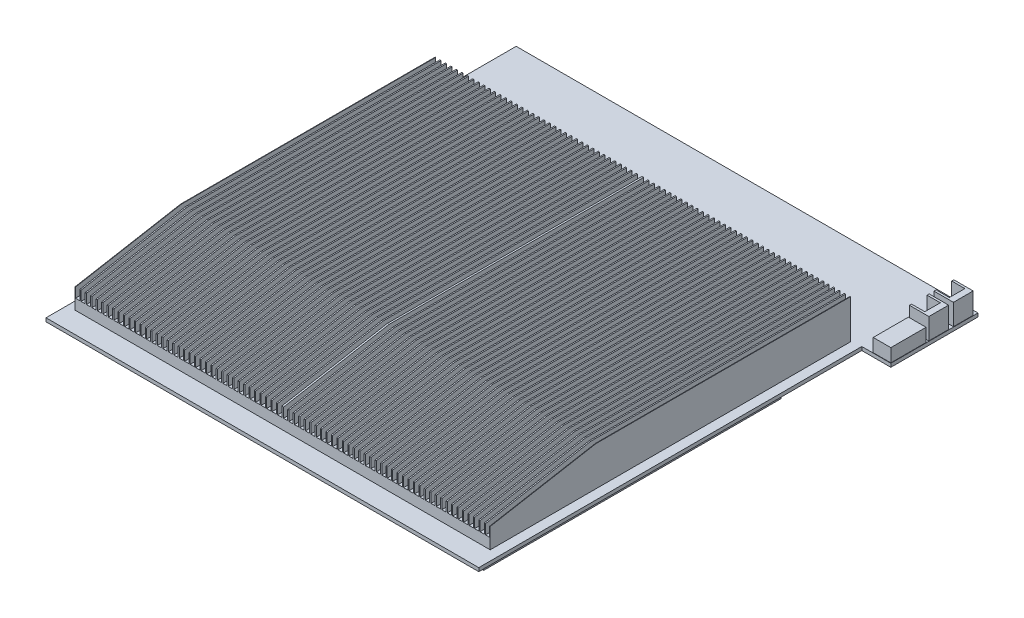
SolidWorks part; units mm, degrees
ref_plane "Front Plane" through (0, 0, 0) normal (0, 0, 1) x (1, 0, 0)
ref_plane "Top Plane" through (0, 0, 0) normal (0, 1, 0) x (1, 0, 0)
ref_plane "Right Plane" through (0, 0, 0) normal (1, 0, 0) x (0, 0, -1)
sketch "Sketch1" plane through (0, 0, 0) normal (0, 1, 0) x (1, 0, 0)
  line L0 (0, 0) -> (0, 267)
  line L1 (0, 267) -> (262.25, 267)
  line L2 (262.25, 267) -> (262.25, 217.5)
  line L3 (262.25, 217.5) -> (245.75, 217.5)
  line L4 (245.75, 217.5) -> (245.75, 0)
  line L5 (245.75, 0) -> (0, 0)
  dimension "D1" = 267
  dimension "D2" = 245.75
  dimension "D3" = 49.5
  dimension "D4" = 16.5
extrude "Boss-Extrude1" add sketch "Sketch1" along normal blind 2
sketch "Sketch2" plane through (0, 2, 0) normal (0, 1, 0) x (1, 0, 0)
  line L0 (245.75, 0) -> (245.75, 217.5) construction
  line L1 (4.5, 216.5) -> (240.25, 216.5)
  line L2 (4.5, 216.5) -> (4.5, 12)
  line L3 (4.5, 12) -> (240.25, 12)
  line L4 (240.25, 216.5) -> (240.25, 12)
  line L5 (4.5, 216.5) -> (240.25, 12) construction
  line L6 (4.5, 12) -> (240.25, 216.5) construction
  line L7 (0, 0) -> (245.75, 0) construction
  line L8 (0, 267) -> (0, 0) construction
  line L9 (262.25, 267) -> (0, 267) construction
  point P4 (122.375, 114.25)
  dimension "D1" = 5.5
  dimension "D2" = 12
  dimension "D3" = 4.5
  dimension "D4" = 50.5
extrude "Boss-Extrude2" add sketch "Sketch2" along normal blind 22.2
sketch "Sketch3" plane through (240.25, 0, 0) normal (1, 0, 0) x (0, 0, -1)
  line L0 (12, 13.5) -> (72, 24.2)
  line L1 (12, 24.2) -> (12, 2) construction
  line L2 (12, 24.2) -> (216.5, 24.2) construction
  line L3 (72, 24.2) -> (12, 24.2)
  line L4 (12, 24.2) -> (12, 13.5)
  dimension "D1" = 60
  dimension "D2" = 10.7
extrude "Cut-Extrude1" cut sketch "Sketch3" against normal up to surface (235.75 mm away) up to face at (4.5, 13.1, -114.25)
sketch "Sketch5" plane through (0, 0, 0) normal (0, -1, 0) x (1, 0, 0)
  line L0 (7.9691, -183.75) -> (7.9691, -14.75)
  line L6 (233.7585, -14.75) -> (233.7585, -183.75)
  line L9 (7.9691, -183.75) -> (67.4691, -183.75)
  line L10 (67.4691, -183.75) -> (67.4691, -216.5)
  line L11 (67.4691, -216.5) -> (174.2585, -216.5)
  line L12 (174.2585, -216.5) -> (174.2585, -183.75)
  line L13 (174.2585, -183.75) -> (233.7585, -183.75)
  line L14 (233.7585, -14.75) -> (7.9691, -14.75)
  line L15 (0, 0) -> (245.75, 0) construction
  line L16 (262.25, -267) -> (0, -267) construction
  line L18 (122.5508, -231.25) -> (149.8508, -231.25)
  line L19 (122.5508, -231.25) -> (122.5508, -261.5)
  line L20 (122.5508, -261.5) -> (149.8508, -261.5)
  line L21 (149.8508, -231.25) -> (149.8508, -261.5)
  line L22 (122.5508, -231.25) -> (149.8508, -261.5) construction
  line L23 (122.5508, -261.5) -> (149.8508, -231.25) construction
  point P16 (136.2008, -246.375)
  dimension "D1" = 14.75
  dimension "D2" = 50.5
  dimension "D3" = 83.25
  dimension "D4" = 59.5
  dimension "D5" = 5.5
  dimension "D6" = 14.75
  dimension "D7" = 27.3
extrude "Boss-Extrude4" add sketch "Sketch5" along normal blind 12.75
sketch "Sketch6" plane through (0, 0, -216.5) normal (0, 0, -1) x (-1, 0, 0)
  line L0 (-122.375, 24.2) -> (-122.375, 2) construction
  line L1 (-240.25, 24.2) -> (-4.5, 24.2) construction
  line L2 (-240.25, 2) -> (-4.5, 2) construction
  line L3 (-262.25, 2) -> (0, 2) construction
  line L4 (-122.875, 24.2) -> (-125.275, 24.2)
  line L5 (-122.875, 24.2) -> (-122.875, 8)
  line L6 (-122.875, 8) -> (-125.275, 8)
  line L7 (-125.275, 24.2) -> (-125.275, 8)
  line L8 (-122.875, 24.2) -> (-125.275, 8) construction
  line L9 (-122.875, 8) -> (-125.275, 24.2) construction
  line L10 (-121.875, 8) -> (-119.475, 24.2) construction
  line L11 (-121.875, 24.2) -> (-119.475, 8) construction
  line L12 (-119.475, 24.2) -> (-119.475, 8)
  line L13 (-121.875, 8) -> (-119.475, 8)
  line L14 (-121.875, 24.2) -> (-121.875, 8)
  line L15 (-121.875, 24.2) -> (-119.475, 24.2)
  line L16 (-125.975, 24.2) -> (-128.375, 24.2)
  line L17 (-125.975, 24.2) -> (-125.975, 8)
  line L18 (-125.975, 8) -> (-128.375, 8)
  line L19 (-128.375, 24.2) -> (-128.375, 8)
  line L20 (-125.975, 24.2) -> (-128.375, 8) construction
  line L21 (-125.975, 8) -> (-128.375, 24.2) construction
  line L22 (-129.075, 24.2) -> (-131.475, 24.2)
  line L23 (-129.075, 24.2) -> (-129.075, 8)
  line L24 (-129.075, 8) -> (-131.475, 8)
  line L25 (-131.475, 24.2) -> (-131.475, 8)
  line L26 (-129.075, 24.2) -> (-131.475, 8) construction
  line L27 (-129.075, 8) -> (-131.475, 24.2) construction
  line L28 (-132.175, 24.2) -> (-134.575, 24.2)
  line L29 (-132.175, 24.2) -> (-132.175, 8)
  line L30 (-132.175, 8) -> (-134.575, 8)
  line L31 (-134.575, 24.2) -> (-134.575, 8)
  line L32 (-132.175, 24.2) -> (-134.575, 8) construction
  line L33 (-132.175, 8) -> (-134.575, 24.2) construction
  line L34 (-135.275, 24.2) -> (-137.675, 24.2)
  line L35 (-135.275, 24.2) -> (-135.275, 8)
  line L36 (-135.275, 8) -> (-137.675, 8)
  line L37 (-137.675, 24.2) -> (-137.675, 8)
  line L38 (-135.275, 24.2) -> (-137.675, 8) construction
  line L39 (-135.275, 8) -> (-137.675, 24.2) construction
  line L40 (-138.375, 24.2) -> (-140.775, 24.2)
  line L41 (-138.375, 24.2) -> (-138.375, 8)
  line L42 (-138.375, 8) -> (-140.775, 8)
  line L43 (-140.775, 24.2) -> (-140.775, 8)
  line L44 (-138.375, 24.2) -> (-140.775, 8) construction
  line L45 (-138.375, 8) -> (-140.775, 24.2) construction
  line L46 (-141.475, 24.2) -> (-143.875, 24.2)
  line L47 (-141.475, 24.2) -> (-141.475, 8)
  line L48 (-141.475, 8) -> (-143.875, 8)
  line L49 (-143.875, 24.2) -> (-143.875, 8)
  line L50 (-141.475, 24.2) -> (-143.875, 8) construction
  line L51 (-141.475, 8) -> (-143.875, 24.2) construction
  line L52 (-144.575, 24.2) -> (-146.975, 24.2)
  line L53 (-144.575, 24.2) -> (-144.575, 8)
  line L54 (-144.575, 8) -> (-146.975, 8)
  line L55 (-146.975, 24.2) -> (-146.975, 8)
  line L56 (-144.575, 24.2) -> (-146.975, 8) construction
  line L57 (-144.575, 8) -> (-146.975, 24.2) construction
  line L58 (-147.675, 24.2) -> (-150.075, 24.2)
  line L59 (-147.675, 24.2) -> (-147.675, 8)
  line L60 (-147.675, 8) -> (-150.075, 8)
  line L61 (-150.075, 24.2) -> (-150.075, 8)
  line L62 (-147.675, 24.2) -> (-150.075, 8) construction
  line L63 (-147.675, 8) -> (-150.075, 24.2) construction
  line L64 (-150.775, 24.2) -> (-153.175, 24.2)
  line L65 (-150.775, 24.2) -> (-150.775, 8)
  line L66 (-150.775, 8) -> (-153.175, 8)
  line L67 (-153.175, 24.2) -> (-153.175, 8)
  line L68 (-150.775, 24.2) -> (-153.175, 8) construction
  line L69 (-150.775, 8) -> (-153.175, 24.2) construction
  line L70 (-153.875, 24.2) -> (-156.275, 24.2)
  line L71 (-153.875, 24.2) -> (-153.875, 8)
  line L72 (-153.875, 8) -> (-156.275, 8)
  line L73 (-156.275, 24.2) -> (-156.275, 8)
  line L74 (-153.875, 24.2) -> (-156.275, 8) construction
  line L75 (-153.875, 8) -> (-156.275, 24.2) construction
  line L76 (-156.975, 24.2) -> (-159.375, 24.2)
  line L77 (-156.975, 24.2) -> (-156.975, 8)
  line L78 (-156.975, 8) -> (-159.375, 8)
  line L79 (-159.375, 24.2) -> (-159.375, 8)
  line L80 (-156.975, 24.2) -> (-159.375, 8) construction
  line L81 (-156.975, 8) -> (-159.375, 24.2) construction
  line L82 (-160.075, 24.2) -> (-162.475, 24.2)
  line L83 (-160.075, 24.2) -> (-160.075, 8)
  line L84 (-160.075, 8) -> (-162.475, 8)
  line L85 (-162.475, 24.2) -> (-162.475, 8)
  line L86 (-160.075, 24.2) -> (-162.475, 8) construction
  line L87 (-160.075, 8) -> (-162.475, 24.2) construction
  line L88 (-163.175, 24.2) -> (-165.575, 24.2)
  line L89 (-163.175, 24.2) -> (-163.175, 8)
  line L90 (-163.175, 8) -> (-165.575, 8)
  line L91 (-165.575, 24.2) -> (-165.575, 8)
  line L92 (-163.175, 24.2) -> (-165.575, 8) construction
  line L93 (-163.175, 8) -> (-165.575, 24.2) construction
  line L94 (-166.275, 24.2) -> (-168.675, 24.2)
  line L95 (-166.275, 24.2) -> (-166.275, 8)
  line L96 (-166.275, 8) -> (-168.675, 8)
  line L97 (-168.675, 24.2) -> (-168.675, 8)
  line L98 (-166.275, 24.2) -> (-168.675, 8) construction
  line L99 (-166.275, 8) -> (-168.675, 24.2) construction
  line L100 (-169.375, 24.2) -> (-171.775, 24.2)
  line L101 (-169.375, 24.2) -> (-169.375, 8)
  line L102 (-169.375, 8) -> (-171.775, 8)
  line L103 (-171.775, 24.2) -> (-171.775, 8)
  line L104 (-169.375, 24.2) -> (-171.775, 8) construction
  line L105 (-169.375, 8) -> (-171.775, 24.2) construction
  line L106 (-172.475, 24.2) -> (-174.875, 24.2)
  line L107 (-172.475, 24.2) -> (-172.475, 8)
  line L108 (-172.475, 8) -> (-174.875, 8)
  line L109 (-174.875, 24.2) -> (-174.875, 8)
  line L110 (-172.475, 24.2) -> (-174.875, 8) construction
  line L111 (-172.475, 8) -> (-174.875, 24.2) construction
  line L112 (-175.575, 24.2) -> (-177.975, 24.2)
  line L113 (-175.575, 24.2) -> (-175.575, 8)
  line L114 (-175.575, 8) -> (-177.975, 8)
  line L115 (-177.975, 24.2) -> (-177.975, 8)
  line L116 (-175.575, 24.2) -> (-177.975, 8) construction
  line L117 (-175.575, 8) -> (-177.975, 24.2) construction
  line L118 (-178.675, 24.2) -> (-181.075, 24.2)
  line L119 (-178.675, 24.2) -> (-178.675, 8)
  line L120 (-178.675, 8) -> (-181.075, 8)
  line L121 (-181.075, 24.2) -> (-181.075, 8)
  line L122 (-178.675, 24.2) -> (-181.075, 8) construction
  line L123 (-178.675, 8) -> (-181.075, 24.2) construction
  line L124 (-181.775, 24.2) -> (-184.175, 24.2)
  line L125 (-181.775, 24.2) -> (-181.775, 8)
  line L126 (-181.775, 8) -> (-184.175, 8)
  line L127 (-184.175, 24.2) -> (-184.175, 8)
  line L128 (-181.775, 24.2) -> (-184.175, 8) construction
  line L129 (-181.775, 8) -> (-184.175, 24.2) construction
  line L130 (-184.875, 24.2) -> (-187.275, 24.2)
  line L131 (-184.875, 24.2) -> (-184.875, 8)
  line L132 (-184.875, 8) -> (-187.275, 8)
  line L133 (-187.275, 24.2) -> (-187.275, 8)
  line L134 (-184.875, 24.2) -> (-187.275, 8) construction
  line L135 (-184.875, 8) -> (-187.275, 24.2) construction
  line L136 (-187.975, 24.2) -> (-190.375, 24.2)
  line L137 (-187.975, 24.2) -> (-187.975, 8)
  line L138 (-187.975, 8) -> (-190.375, 8)
  line L139 (-190.375, 24.2) -> (-190.375, 8)
  line L140 (-187.975, 24.2) -> (-190.375, 8) construction
  line L141 (-187.975, 8) -> (-190.375, 24.2) construction
  line L142 (-191.075, 24.2) -> (-193.475, 24.2)
  line L143 (-191.075, 24.2) -> (-191.075, 8)
  line L144 (-191.075, 8) -> (-193.475, 8)
  line L145 (-193.475, 24.2) -> (-193.475, 8)
  line L146 (-191.075, 24.2) -> (-193.475, 8) construction
  line L147 (-191.075, 8) -> (-193.475, 24.2) construction
  line L148 (-194.175, 24.2) -> (-196.575, 24.2)
  line L149 (-194.175, 24.2) -> (-194.175, 8)
  line L150 (-194.175, 8) -> (-196.575, 8)
  line L151 (-196.575, 24.2) -> (-196.575, 8)
  line L152 (-194.175, 24.2) -> (-196.575, 8) construction
  line L153 (-194.175, 8) -> (-196.575, 24.2) construction
  line L154 (-197.275, 24.2) -> (-199.675, 24.2)
  line L155 (-197.275, 24.2) -> (-197.275, 8)
  line L156 (-197.275, 8) -> (-199.675, 8)
  line L157 (-199.675, 24.2) -> (-199.675, 8)
  line L158 (-197.275, 24.2) -> (-199.675, 8) construction
  line L159 (-197.275, 8) -> (-199.675, 24.2) construction
  line L160 (-200.375, 24.2) -> (-202.775, 24.2)
  line L161 (-200.375, 24.2) -> (-200.375, 8)
  line L162 (-200.375, 8) -> (-202.775, 8)
  line L163 (-202.775, 24.2) -> (-202.775, 8)
  line L164 (-200.375, 24.2) -> (-202.775, 8) construction
  line L165 (-200.375, 8) -> (-202.775, 24.2) construction
  line L166 (-203.475, 24.2) -> (-205.875, 24.2)
  line L167 (-203.475, 24.2) -> (-203.475, 8)
  line L168 (-203.475, 8) -> (-205.875, 8)
  line L169 (-205.875, 24.2) -> (-205.875, 8)
  line L170 (-203.475, 24.2) -> (-205.875, 8) construction
  line L171 (-203.475, 8) -> (-205.875, 24.2) construction
  line L172 (-206.575, 24.2) -> (-208.975, 24.2)
  line L173 (-206.575, 24.2) -> (-206.575, 8)
  line L174 (-206.575, 8) -> (-208.975, 8)
  line L175 (-208.975, 24.2) -> (-208.975, 8)
  line L176 (-206.575, 24.2) -> (-208.975, 8) construction
  line L177 (-206.575, 8) -> (-208.975, 24.2) construction
  line L178 (-209.675, 24.2) -> (-212.075, 24.2)
  line L179 (-209.675, 24.2) -> (-209.675, 8)
  line L180 (-209.675, 8) -> (-212.075, 8)
  line L181 (-212.075, 24.2) -> (-212.075, 8)
  line L182 (-209.675, 24.2) -> (-212.075, 8) construction
  line L183 (-209.675, 8) -> (-212.075, 24.2) construction
  line L184 (-212.775, 24.2) -> (-215.175, 24.2)
  line L185 (-212.775, 24.2) -> (-212.775, 8)
  line L186 (-212.775, 8) -> (-215.175, 8)
  line L187 (-215.175, 24.2) -> (-215.175, 8)
  line L188 (-212.775, 24.2) -> (-215.175, 8) construction
  line L189 (-212.775, 8) -> (-215.175, 24.2) construction
  line L190 (-215.875, 24.2) -> (-218.275, 24.2)
  line L191 (-215.875, 24.2) -> (-215.875, 8)
  line L192 (-215.875, 8) -> (-218.275, 8)
  line L193 (-218.275, 24.2) -> (-218.275, 8)
  line L194 (-215.875, 24.2) -> (-218.275, 8) construction
  line L195 (-215.875, 8) -> (-218.275, 24.2) construction
  line L196 (-218.975, 24.2) -> (-221.375, 24.2)
  line L197 (-218.975, 24.2) -> (-218.975, 8)
  line L198 (-218.975, 8) -> (-221.375, 8)
  line L199 (-221.375, 24.2) -> (-221.375, 8)
  line L200 (-218.975, 24.2) -> (-221.375, 8) construction
  line L201 (-218.975, 8) -> (-221.375, 24.2) construction
  line L202 (-222.075, 24.2) -> (-224.475, 24.2)
  line L203 (-222.075, 24.2) -> (-222.075, 8)
  line L204 (-222.075, 8) -> (-224.475, 8)
  line L205 (-224.475, 24.2) -> (-224.475, 8)
  line L206 (-222.075, 24.2) -> (-224.475, 8) construction
  line L207 (-222.075, 8) -> (-224.475, 24.2) construction
  line L208 (-225.175, 24.2) -> (-227.575, 24.2)
  line L209 (-225.175, 24.2) -> (-225.175, 8)
  line L210 (-225.175, 8) -> (-227.575, 8)
  line L211 (-227.575, 24.2) -> (-227.575, 8)
  line L212 (-225.175, 24.2) -> (-227.575, 8) construction
  line L213 (-225.175, 8) -> (-227.575, 24.2) construction
  line L214 (-228.275, 24.2) -> (-230.675, 24.2)
  line L215 (-228.275, 24.2) -> (-228.275, 8)
  line L216 (-228.275, 8) -> (-230.675, 8)
  line L217 (-230.675, 24.2) -> (-230.675, 8)
  line L218 (-228.275, 24.2) -> (-230.675, 8) construction
  line L219 (-228.275, 8) -> (-230.675, 24.2) construction
  line L220 (-231.375, 24.2) -> (-233.775, 24.2)
  line L221 (-231.375, 24.2) -> (-231.375, 8)
  line L222 (-231.375, 8) -> (-233.775, 8)
  line L223 (-233.775, 24.2) -> (-233.775, 8)
  line L224 (-231.375, 24.2) -> (-233.775, 8) construction
  line L225 (-231.375, 8) -> (-233.775, 24.2) construction
  line L226 (-234.475, 24.2) -> (-236.875, 24.2)
  line L227 (-234.475, 24.2) -> (-234.475, 8)
  line L228 (-234.475, 8) -> (-236.875, 8)
  line L229 (-236.875, 24.2) -> (-236.875, 8)
  line L230 (-234.475, 24.2) -> (-236.875, 8) construction
  line L231 (-234.475, 8) -> (-236.875, 24.2) construction
  line L232 (-237.575, 24.2) -> (-239.975, 24.2)
  line L233 (-237.575, 24.2) -> (-237.575, 8)
  line L234 (-237.575, 8) -> (-239.975, 8)
  line L235 (-239.975, 24.2) -> (-239.975, 8)
  line L236 (-237.575, 24.2) -> (-239.975, 8) construction
  line L237 (-237.575, 8) -> (-239.975, 24.2) construction
  line L238 (-116.375, 24.2) -> (-116.375, 8)
  line L239 (-118.775, 8) -> (-116.375, 8)
  line L240 (-118.775, 24.2) -> (-118.775, 8)
  line L241 (-118.775, 24.2) -> (-116.375, 24.2)
  line L242 (-118.775, 8) -> (-116.375, 24.2) construction
  line L243 (-118.775, 24.2) -> (-116.375, 8) construction
  line L244 (-113.275, 24.2) -> (-113.275, 8)
  line L245 (-115.675, 8) -> (-113.275, 8)
  line L246 (-115.675, 24.2) -> (-115.675, 8)
  line L247 (-115.675, 24.2) -> (-113.275, 24.2)
  line L248 (-115.675, 8) -> (-113.275, 24.2) construction
  line L249 (-115.675, 24.2) -> (-113.275, 8) construction
  line L250 (-110.175, 24.2) -> (-110.175, 8)
  line L251 (-112.575, 8) -> (-110.175, 8)
  line L252 (-112.575, 24.2) -> (-112.575, 8)
  line L253 (-112.575, 24.2) -> (-110.175, 24.2)
  line L254 (-112.575, 8) -> (-110.175, 24.2) construction
  line L255 (-112.575, 24.2) -> (-110.175, 8) construction
  line L256 (-107.075, 24.2) -> (-107.075, 8)
  line L257 (-109.475, 8) -> (-107.075, 8)
  line L258 (-109.475, 24.2) -> (-109.475, 8)
  line L259 (-109.475, 24.2) -> (-107.075, 24.2)
  line L260 (-109.475, 8) -> (-107.075, 24.2) construction
  line L261 (-109.475, 24.2) -> (-107.075, 8) construction
  line L262 (-103.975, 24.2) -> (-103.975, 8)
  line L263 (-106.375, 8) -> (-103.975, 8)
  line L264 (-106.375, 24.2) -> (-106.375, 8)
  line L265 (-106.375, 24.2) -> (-103.975, 24.2)
  line L266 (-106.375, 8) -> (-103.975, 24.2) construction
  line L267 (-106.375, 24.2) -> (-103.975, 8) construction
  line L268 (-100.875, 24.2) -> (-100.875, 8)
  line L269 (-103.275, 8) -> (-100.875, 8)
  line L270 (-103.275, 24.2) -> (-103.275, 8)
  line L271 (-103.275, 24.2) -> (-100.875, 24.2)
  line L272 (-103.275, 8) -> (-100.875, 24.2) construction
  line L273 (-103.275, 24.2) -> (-100.875, 8) construction
  line L274 (-97.775, 24.2) -> (-97.775, 8)
  line L275 (-100.175, 8) -> (-97.775, 8)
  line L276 (-100.175, 24.2) -> (-100.175, 8)
  line L277 (-100.175, 24.2) -> (-97.775, 24.2)
  line L278 (-100.175, 8) -> (-97.775, 24.2) construction
  line L279 (-100.175, 24.2) -> (-97.775, 8) construction
  line L280 (-94.675, 24.2) -> (-94.675, 8)
  line L281 (-97.075, 8) -> (-94.675, 8)
  line L282 (-97.075, 24.2) -> (-97.075, 8)
  line L283 (-97.075, 24.2) -> (-94.675, 24.2)
  line L284 (-97.075, 8) -> (-94.675, 24.2) construction
  line L285 (-97.075, 24.2) -> (-94.675, 8) construction
  line L286 (-91.575, 24.2) -> (-91.575, 8)
  line L287 (-93.975, 8) -> (-91.575, 8)
  line L288 (-93.975, 24.2) -> (-93.975, 8)
  line L289 (-93.975, 24.2) -> (-91.575, 24.2)
  line L290 (-93.975, 8) -> (-91.575, 24.2) construction
  line L291 (-93.975, 24.2) -> (-91.575, 8) construction
  line L292 (-88.475, 24.2) -> (-88.475, 8)
  line L293 (-90.875, 8) -> (-88.475, 8)
  line L294 (-90.875, 24.2) -> (-90.875, 8)
  line L295 (-90.875, 24.2) -> (-88.475, 24.2)
  line L296 (-90.875, 8) -> (-88.475, 24.2) construction
  line L297 (-90.875, 24.2) -> (-88.475, 8) construction
  line L298 (-85.375, 24.2) -> (-85.375, 8)
  line L299 (-87.775, 8) -> (-85.375, 8)
  line L300 (-87.775, 24.2) -> (-87.775, 8)
  line L301 (-87.775, 24.2) -> (-85.375, 24.2)
  line L302 (-87.775, 8) -> (-85.375, 24.2) construction
  line L303 (-87.775, 24.2) -> (-85.375, 8) construction
  line L304 (-82.275, 24.2) -> (-82.275, 8)
  line L305 (-84.675, 8) -> (-82.275, 8)
  line L306 (-84.675, 24.2) -> (-84.675, 8)
  line L307 (-84.675, 24.2) -> (-82.275, 24.2)
  line L308 (-84.675, 8) -> (-82.275, 24.2) construction
  line L309 (-84.675, 24.2) -> (-82.275, 8) construction
  line L310 (-79.175, 24.2) -> (-79.175, 8)
  line L311 (-81.575, 8) -> (-79.175, 8)
  line L312 (-81.575, 24.2) -> (-81.575, 8)
  line L313 (-81.575, 24.2) -> (-79.175, 24.2)
  line L314 (-81.575, 8) -> (-79.175, 24.2) construction
  line L315 (-81.575, 24.2) -> (-79.175, 8) construction
  line L316 (-76.075, 24.2) -> (-76.075, 8)
  line L317 (-78.475, 8) -> (-76.075, 8)
  line L318 (-78.475, 24.2) -> (-78.475, 8)
  line L319 (-78.475, 24.2) -> (-76.075, 24.2)
  line L320 (-78.475, 8) -> (-76.075, 24.2) construction
  line L321 (-78.475, 24.2) -> (-76.075, 8) construction
  line L322 (-72.975, 24.2) -> (-72.975, 8)
  line L323 (-75.375, 8) -> (-72.975, 8)
  line L324 (-75.375, 24.2) -> (-75.375, 8)
  line L325 (-75.375, 24.2) -> (-72.975, 24.2)
  line L326 (-75.375, 8) -> (-72.975, 24.2) construction
  line L327 (-75.375, 24.2) -> (-72.975, 8) construction
  line L328 (-69.875, 24.2) -> (-69.875, 8)
  line L329 (-72.275, 8) -> (-69.875, 8)
  line L330 (-72.275, 24.2) -> (-72.275, 8)
  line L331 (-72.275, 24.2) -> (-69.875, 24.2)
  line L332 (-72.275, 8) -> (-69.875, 24.2) construction
  line L333 (-72.275, 24.2) -> (-69.875, 8) construction
  line L334 (-66.775, 24.2) -> (-66.775, 8)
  line L335 (-69.175, 8) -> (-66.775, 8)
  line L336 (-69.175, 24.2) -> (-69.175, 8)
  line L337 (-69.175, 24.2) -> (-66.775, 24.2)
  line L338 (-69.175, 8) -> (-66.775, 24.2) construction
  line L339 (-69.175, 24.2) -> (-66.775, 8) construction
  line L340 (-63.675, 24.2) -> (-63.675, 8)
  line L341 (-66.075, 8) -> (-63.675, 8)
  line L342 (-66.075, 24.2) -> (-66.075, 8)
  line L343 (-66.075, 24.2) -> (-63.675, 24.2)
  line L344 (-66.075, 8) -> (-63.675, 24.2) construction
  line L345 (-66.075, 24.2) -> (-63.675, 8) construction
  line L346 (-60.575, 24.2) -> (-60.575, 8)
  line L347 (-62.975, 8) -> (-60.575, 8)
  line L348 (-62.975, 24.2) -> (-62.975, 8)
  line L349 (-62.975, 24.2) -> (-60.575, 24.2)
  line L350 (-62.975, 8) -> (-60.575, 24.2) construction
  line L351 (-62.975, 24.2) -> (-60.575, 8) construction
  line L352 (-57.475, 24.2) -> (-57.475, 8)
  line L353 (-59.875, 8) -> (-57.475, 8)
  line L354 (-59.875, 24.2) -> (-59.875, 8)
  line L355 (-59.875, 24.2) -> (-57.475, 24.2)
  line L356 (-59.875, 8) -> (-57.475, 24.2) construction
  line L357 (-59.875, 24.2) -> (-57.475, 8) construction
  line L358 (-54.375, 24.2) -> (-54.375, 8)
  line L359 (-56.775, 8) -> (-54.375, 8)
  line L360 (-56.775, 24.2) -> (-56.775, 8)
  line L361 (-56.775, 24.2) -> (-54.375, 24.2)
  line L362 (-56.775, 8) -> (-54.375, 24.2) construction
  line L363 (-56.775, 24.2) -> (-54.375, 8) construction
  line L364 (-51.275, 24.2) -> (-51.275, 8)
  line L365 (-53.675, 8) -> (-51.275, 8)
  line L366 (-53.675, 24.2) -> (-53.675, 8)
  line L367 (-53.675, 24.2) -> (-51.275, 24.2)
  line L368 (-53.675, 8) -> (-51.275, 24.2) construction
  line L369 (-53.675, 24.2) -> (-51.275, 8) construction
  line L370 (-48.175, 24.2) -> (-48.175, 8)
  line L371 (-50.575, 8) -> (-48.175, 8)
  line L372 (-50.575, 24.2) -> (-50.575, 8)
  line L373 (-50.575, 24.2) -> (-48.175, 24.2)
  line L374 (-50.575, 8) -> (-48.175, 24.2) construction
  line L375 (-50.575, 24.2) -> (-48.175, 8) construction
  line L376 (-45.075, 24.2) -> (-45.075, 8)
  line L377 (-47.475, 8) -> (-45.075, 8)
  line L378 (-47.475, 24.2) -> (-47.475, 8)
  line L379 (-47.475, 24.2) -> (-45.075, 24.2)
  line L380 (-47.475, 8) -> (-45.075, 24.2) construction
  line L381 (-47.475, 24.2) -> (-45.075, 8) construction
  line L382 (-41.975, 24.2) -> (-41.975, 8)
  line L383 (-44.375, 8) -> (-41.975, 8)
  line L384 (-44.375, 24.2) -> (-44.375, 8)
  line L385 (-44.375, 24.2) -> (-41.975, 24.2)
  line L386 (-44.375, 8) -> (-41.975, 24.2) construction
  line L387 (-44.375, 24.2) -> (-41.975, 8) construction
  line L388 (-38.875, 24.2) -> (-38.875, 8)
  line L389 (-41.275, 8) -> (-38.875, 8)
  line L390 (-41.275, 24.2) -> (-41.275, 8)
  line L391 (-41.275, 24.2) -> (-38.875, 24.2)
  line L392 (-41.275, 8) -> (-38.875, 24.2) construction
  line L393 (-41.275, 24.2) -> (-38.875, 8) construction
  line L394 (-35.775, 24.2) -> (-35.775, 8)
  line L395 (-38.175, 8) -> (-35.775, 8)
  line L396 (-38.175, 24.2) -> (-38.175, 8)
  line L397 (-38.175, 24.2) -> (-35.775, 24.2)
  line L398 (-38.175, 8) -> (-35.775, 24.2) construction
  line L399 (-38.175, 24.2) -> (-35.775, 8) construction
  line L400 (-32.675, 24.2) -> (-32.675, 8)
  line L401 (-35.075, 8) -> (-32.675, 8)
  line L402 (-35.075, 24.2) -> (-35.075, 8)
  line L403 (-35.075, 24.2) -> (-32.675, 24.2)
  line L404 (-35.075, 8) -> (-32.675, 24.2) construction
  line L405 (-35.075, 24.2) -> (-32.675, 8) construction
  line L406 (-29.575, 24.2) -> (-29.575, 8)
  line L407 (-31.975, 8) -> (-29.575, 8)
  line L408 (-31.975, 24.2) -> (-31.975, 8)
  line L409 (-31.975, 24.2) -> (-29.575, 24.2)
  line L410 (-31.975, 8) -> (-29.575, 24.2) construction
  line L411 (-31.975, 24.2) -> (-29.575, 8) construction
  line L412 (-26.475, 24.2) -> (-26.475, 8)
  line L413 (-28.875, 8) -> (-26.475, 8)
  line L414 (-28.875, 24.2) -> (-28.875, 8)
  line L415 (-28.875, 24.2) -> (-26.475, 24.2)
  line L416 (-28.875, 8) -> (-26.475, 24.2) construction
  line L417 (-28.875, 24.2) -> (-26.475, 8) construction
  line L418 (-23.375, 24.2) -> (-23.375, 8)
  line L419 (-25.775, 8) -> (-23.375, 8)
  line L420 (-25.775, 24.2) -> (-25.775, 8)
  line L421 (-25.775, 24.2) -> (-23.375, 24.2)
  line L422 (-25.775, 8) -> (-23.375, 24.2) construction
  line L423 (-25.775, 24.2) -> (-23.375, 8) construction
  line L424 (-20.275, 24.2) -> (-20.275, 8)
  line L425 (-22.675, 8) -> (-20.275, 8)
  line L426 (-22.675, 24.2) -> (-22.675, 8)
  line L427 (-22.675, 24.2) -> (-20.275, 24.2)
  line L428 (-22.675, 8) -> (-20.275, 24.2) construction
  line L429 (-22.675, 24.2) -> (-20.275, 8) construction
  line L430 (-17.175, 24.2) -> (-17.175, 8)
  line L431 (-19.575, 8) -> (-17.175, 8)
  line L432 (-19.575, 24.2) -> (-19.575, 8)
  line L433 (-19.575, 24.2) -> (-17.175, 24.2)
  line L434 (-19.575, 8) -> (-17.175, 24.2) construction
  line L435 (-19.575, 24.2) -> (-17.175, 8) construction
  line L436 (-14.075, 24.2) -> (-14.075, 8)
  line L437 (-16.475, 8) -> (-14.075, 8)
  line L438 (-16.475, 24.2) -> (-16.475, 8)
  line L439 (-16.475, 24.2) -> (-14.075, 24.2)
  line L440 (-16.475, 8) -> (-14.075, 24.2) construction
  line L441 (-16.475, 24.2) -> (-14.075, 8) construction
  line L442 (-10.975, 24.2) -> (-10.975, 8)
  line L443 (-13.375, 8) -> (-10.975, 8)
  line L444 (-13.375, 24.2) -> (-13.375, 8)
  line L445 (-13.375, 24.2) -> (-10.975, 24.2)
  line L446 (-13.375, 8) -> (-10.975, 24.2) construction
  line L447 (-13.375, 24.2) -> (-10.975, 8) construction
  line L448 (-7.875, 24.2) -> (-7.875, 8)
  line L449 (-10.275, 8) -> (-7.875, 8)
  line L450 (-10.275, 24.2) -> (-10.275, 8)
  line L451 (-10.275, 24.2) -> (-7.875, 24.2)
  line L452 (-10.275, 8) -> (-7.875, 24.2) construction
  line L453 (-10.275, 24.2) -> (-7.875, 8) construction
  line L454 (-4.775, 24.2) -> (-4.775, 8)
  line L455 (-7.175, 8) -> (-4.775, 8)
  line L456 (-7.175, 24.2) -> (-7.175, 8)
  line L457 (-7.175, 24.2) -> (-4.775, 24.2)
  line L458 (-7.175, 8) -> (-4.775, 24.2) construction
  line L459 (-7.175, 24.2) -> (-4.775, 8) construction
  point P10 (-124.075, 16.1)
  point P17 (-120.675, 16.1)
  point P23 (-127.175, 16.1)
  point P28 (-130.275, 16.1)
  point P33 (-133.375, 16.1)
  point P38 (-136.475, 16.1)
  point P43 (-139.575, 16.1)
  point P48 (-142.675, 16.1)
  point P53 (-145.775, 16.1)
  point P58 (-148.875, 16.1)
  point P63 (-151.975, 16.1)
  point P68 (-155.075, 16.1)
  point P73 (-158.175, 16.1)
  point P78 (-161.275, 16.1)
  point P83 (-164.375, 16.1)
  point P88 (-167.475, 16.1)
  point P93 (-170.575, 16.1)
  point P98 (-173.675, 16.1)
  point P103 (-176.775, 16.1)
  point P108 (-179.875, 16.1)
  point P113 (-182.975, 16.1)
  point P118 (-186.075, 16.1)
  point P123 (-189.175, 16.1)
  point P128 (-192.275, 16.1)
  point P133 (-195.375, 16.1)
  point P138 (-198.475, 16.1)
  point P143 (-201.575, 16.1)
  point P148 (-204.675, 16.1)
  point P153 (-207.775, 16.1)
  point P158 (-210.875, 16.1)
  point P163 (-213.975, 16.1)
  point P168 (-217.075, 16.1)
  point P173 (-220.175, 16.1)
  point P178 (-223.275, 16.1)
  point P183 (-226.375, 16.1)
  point P188 (-229.475, 16.1)
  point P193 (-232.575, 16.1)
  point P198 (-235.675, 16.1)
  point P203 (-238.775, 16.1)
  point P209 (-117.575, 16.1)
  point P214 (-114.475, 16.1)
  point P219 (-111.375, 16.1)
  point P224 (-108.275, 16.1)
  point P229 (-105.175, 16.1)
  point P234 (-102.075, 16.1)
  point P239 (-98.975, 16.1)
  point P244 (-95.875, 16.1)
  point P249 (-92.775, 16.1)
  point P254 (-89.675, 16.1)
  point P259 (-86.575, 16.1)
  point P264 (-83.475, 16.1)
  point P269 (-80.375, 16.1)
  point P274 (-77.275, 16.1)
  point P279 (-74.175, 16.1)
  point P284 (-71.075, 16.1)
  point P289 (-67.975, 16.1)
  point P294 (-64.875, 16.1)
  point P299 (-61.775, 16.1)
  point P304 (-58.675, 16.1)
  point P309 (-55.575, 16.1)
  point P314 (-52.475, 16.1)
  point P319 (-49.375, 16.1)
  point P324 (-46.275, 16.1)
  point P329 (-43.175, 16.1)
  point P334 (-40.075, 16.1)
  point P339 (-36.975, 16.1)
  point P344 (-33.875, 16.1)
  point P349 (-30.775, 16.1)
  point P354 (-27.675, 16.1)
  point P359 (-24.575, 16.1)
  point P364 (-21.475, 16.1)
  point P369 (-18.375, 16.1)
  point P374 (-15.275, 16.1)
  point P379 (-12.175, 16.1)
  point P384 (-9.075, 16.1)
  point P389 (-5.975, 16.1)
  dimension "D1" = 1
  dimension "D2" = 6
  dimension "D3" = 2.4
  dimension "D4" = 38
  dimension "D5" = 38
extrude "Cut-Extrude2" cut sketch "Sketch6" against normal through all
sketch "Sketch7" plane through (0, 0, -14.75) normal (0, 0, 1) x (1, 0, 0)
  line L0 (120.8638, 0) -> (120.8638, -12.75) construction
  line L1 (233.7585, 0) -> (7.9691, 0) construction
  line L2 (233.7585, -12.75) -> (7.9691, -12.75) construction
  line L3 (121.8638, -1.9399) -> (124.2638, -12.75) construction
  line L4 (119.8638, -12.75) -> (117.4638, -12.75)
  line L5 (119.8638, -12.75) -> (119.8638, -1.9399)
  line L6 (119.8638, -1.9399) -> (117.4638, -1.9399)
  line L7 (117.4638, -12.75) -> (117.4638, -1.9399)
  line L8 (119.8638, -12.75) -> (117.4638, -1.9399) construction
  line L9 (119.8638, -1.9399) -> (117.4638, -12.75) construction
  line L10 (121.8638, -12.75) -> (124.2638, -1.9399) construction
  line L11 (124.2638, -12.75) -> (124.2638, -1.9399)
  line L12 (121.8638, -1.9399) -> (124.2638, -1.9399)
  line L13 (121.8638, -12.75) -> (121.8638, -1.9399)
  line L14 (121.8638, -12.75) -> (124.2638, -12.75)
  line L15 (127.3638, -12.75) -> (127.3638, -1.9399)
  line L16 (124.9638, -1.9399) -> (127.3638, -1.9399)
  line L17 (124.9638, -12.75) -> (124.9638, -1.9399)
  line L18 (124.9638, -12.75) -> (127.3638, -12.75)
  line L19 (124.9638, -1.9399) -> (127.3638, -12.75) construction
  line L20 (124.9638, -12.75) -> (127.3638, -1.9399) construction
  line L21 (130.4638, -12.75) -> (130.4638, -1.9399)
  line L22 (128.0638, -1.9399) -> (130.4638, -1.9399)
  line L23 (128.0638, -12.75) -> (128.0638, -1.9399)
  line L24 (128.0638, -12.75) -> (130.4638, -12.75)
  line L25 (128.0638, -1.9399) -> (130.4638, -12.75) construction
  line L26 (128.0638, -12.75) -> (130.4638, -1.9399) construction
  line L27 (133.5638, -12.75) -> (133.5638, -1.9399)
  line L28 (131.1638, -1.9399) -> (133.5638, -1.9399)
  line L29 (131.1638, -12.75) -> (131.1638, -1.9399)
  line L30 (131.1638, -12.75) -> (133.5638, -12.75)
  line L31 (131.1638, -1.9399) -> (133.5638, -12.75) construction
  line L32 (131.1638, -12.75) -> (133.5638, -1.9399) construction
  line L33 (136.6638, -12.75) -> (136.6638, -1.9399)
  line L34 (134.2638, -1.9399) -> (136.6638, -1.9399)
  line L35 (134.2638, -12.75) -> (134.2638, -1.9399)
  line L36 (134.2638, -12.75) -> (136.6638, -12.75)
  line L37 (134.2638, -1.9399) -> (136.6638, -12.75) construction
  line L38 (134.2638, -12.75) -> (136.6638, -1.9399) construction
  line L39 (139.7638, -12.75) -> (139.7638, -1.9399)
  line L40 (137.3638, -1.9399) -> (139.7638, -1.9399)
  line L41 (137.3638, -12.75) -> (137.3638, -1.9399)
  line L42 (137.3638, -12.75) -> (139.7638, -12.75)
  line L43 (137.3638, -1.9399) -> (139.7638, -12.75) construction
  line L44 (137.3638, -12.75) -> (139.7638, -1.9399) construction
  line L45 (142.8638, -12.75) -> (142.8638, -1.9399)
  line L46 (140.4638, -1.9399) -> (142.8638, -1.9399)
  line L47 (140.4638, -12.75) -> (140.4638, -1.9399)
  line L48 (140.4638, -12.75) -> (142.8638, -12.75)
  line L49 (140.4638, -1.9399) -> (142.8638, -12.75) construction
  line L50 (140.4638, -12.75) -> (142.8638, -1.9399) construction
  line L51 (145.9638, -12.75) -> (145.9638, -1.9399)
  line L52 (143.5638, -1.9399) -> (145.9638, -1.9399)
  line L53 (143.5638, -12.75) -> (143.5638, -1.9399)
  line L54 (143.5638, -12.75) -> (145.9638, -12.75)
  line L55 (143.5638, -1.9399) -> (145.9638, -12.75) construction
  line L56 (143.5638, -12.75) -> (145.9638, -1.9399) construction
  line L57 (149.0638, -12.75) -> (149.0638, -1.9399)
  line L58 (146.6638, -1.9399) -> (149.0638, -1.9399)
  line L59 (146.6638, -12.75) -> (146.6638, -1.9399)
  line L60 (146.6638, -12.75) -> (149.0638, -12.75)
  line L61 (146.6638, -1.9399) -> (149.0638, -12.75) construction
  line L62 (146.6638, -12.75) -> (149.0638, -1.9399) construction
  line L63 (152.1638, -12.75) -> (152.1638, -1.9399)
  line L64 (149.7638, -1.9399) -> (152.1638, -1.9399)
  line L65 (149.7638, -12.75) -> (149.7638, -1.9399)
  line L66 (149.7638, -12.75) -> (152.1638, -12.75)
  line L67 (149.7638, -1.9399) -> (152.1638, -12.75) construction
  line L68 (149.7638, -12.75) -> (152.1638, -1.9399) construction
  line L69 (155.2638, -12.75) -> (155.2638, -1.9399)
  line L70 (152.8638, -1.9399) -> (155.2638, -1.9399)
  line L71 (152.8638, -12.75) -> (152.8638, -1.9399)
  line L72 (152.8638, -12.75) -> (155.2638, -12.75)
  line L73 (152.8638, -1.9399) -> (155.2638, -12.75) construction
  line L74 (152.8638, -12.75) -> (155.2638, -1.9399) construction
  line L75 (158.3638, -12.75) -> (158.3638, -1.9399)
  line L76 (155.9638, -1.9399) -> (158.3638, -1.9399)
  line L77 (155.9638, -12.75) -> (155.9638, -1.9399)
  line L78 (155.9638, -12.75) -> (158.3638, -12.75)
  line L79 (155.9638, -1.9399) -> (158.3638, -12.75) construction
  line L80 (155.9638, -12.75) -> (158.3638, -1.9399) construction
  line L81 (161.4638, -12.75) -> (161.4638, -1.9399)
  line L82 (159.0638, -1.9399) -> (161.4638, -1.9399)
  line L83 (159.0638, -12.75) -> (159.0638, -1.9399)
  line L84 (159.0638, -12.75) -> (161.4638, -12.75)
  line L85 (159.0638, -1.9399) -> (161.4638, -12.75) construction
  line L86 (159.0638, -12.75) -> (161.4638, -1.9399) construction
  line L87 (164.5638, -12.75) -> (164.5638, -1.9399)
  line L88 (162.1638, -1.9399) -> (164.5638, -1.9399)
  line L89 (162.1638, -12.75) -> (162.1638, -1.9399)
  line L90 (162.1638, -12.75) -> (164.5638, -12.75)
  line L91 (162.1638, -1.9399) -> (164.5638, -12.75) construction
  line L92 (162.1638, -12.75) -> (164.5638, -1.9399) construction
  line L93 (167.6638, -12.75) -> (167.6638, -1.9399)
  line L94 (165.2638, -1.9399) -> (167.6638, -1.9399)
  line L95 (165.2638, -12.75) -> (165.2638, -1.9399)
  line L96 (165.2638, -12.75) -> (167.6638, -12.75)
  line L97 (165.2638, -1.9399) -> (167.6638, -12.75) construction
  line L98 (165.2638, -12.75) -> (167.6638, -1.9399) construction
  line L99 (170.7638, -12.75) -> (170.7638, -1.9399)
  line L100 (168.3638, -1.9399) -> (170.7638, -1.9399)
  line L101 (168.3638, -12.75) -> (168.3638, -1.9399)
  line L102 (168.3638, -12.75) -> (170.7638, -12.75)
  line L103 (168.3638, -1.9399) -> (170.7638, -12.75) construction
  line L104 (168.3638, -12.75) -> (170.7638, -1.9399) construction
  line L105 (173.8638, -12.75) -> (173.8638, -1.9399)
  line L106 (171.4638, -1.9399) -> (173.8638, -1.9399)
  line L107 (171.4638, -12.75) -> (171.4638, -1.9399)
  line L108 (171.4638, -12.75) -> (173.8638, -12.75)
  line L109 (171.4638, -1.9399) -> (173.8638, -12.75) construction
  line L110 (171.4638, -12.75) -> (173.8638, -1.9399) construction
  line L111 (176.9638, -12.75) -> (176.9638, -1.9399)
  line L112 (174.5638, -1.9399) -> (176.9638, -1.9399)
  line L113 (174.5638, -12.75) -> (174.5638, -1.9399)
  line L114 (174.5638, -12.75) -> (176.9638, -12.75)
  line L115 (174.5638, -1.9399) -> (176.9638, -12.75) construction
  line L116 (174.5638, -12.75) -> (176.9638, -1.9399) construction
  line L117 (180.0638, -12.75) -> (180.0638, -1.9399)
  line L118 (177.6638, -1.9399) -> (180.0638, -1.9399)
  line L119 (177.6638, -12.75) -> (177.6638, -1.9399)
  line L120 (177.6638, -12.75) -> (180.0638, -12.75)
  line L121 (177.6638, -1.9399) -> (180.0638, -12.75) construction
  line L122 (177.6638, -12.75) -> (180.0638, -1.9399) construction
  line L123 (183.1638, -12.75) -> (183.1638, -1.9399)
  line L124 (180.7638, -1.9399) -> (183.1638, -1.9399)
  line L125 (180.7638, -12.75) -> (180.7638, -1.9399)
  line L126 (180.7638, -12.75) -> (183.1638, -12.75)
  line L127 (180.7638, -1.9399) -> (183.1638, -12.75) construction
  line L128 (180.7638, -12.75) -> (183.1638, -1.9399) construction
  line L129 (186.2638, -12.75) -> (186.2638, -1.9399)
  line L130 (183.8638, -1.9399) -> (186.2638, -1.9399)
  line L131 (183.8638, -12.75) -> (183.8638, -1.9399)
  line L132 (183.8638, -12.75) -> (186.2638, -12.75)
  line L133 (183.8638, -1.9399) -> (186.2638, -12.75) construction
  line L134 (183.8638, -12.75) -> (186.2638, -1.9399) construction
  line L135 (189.3638, -12.75) -> (189.3638, -1.9399)
  line L136 (186.9638, -1.9399) -> (189.3638, -1.9399)
  line L137 (186.9638, -12.75) -> (186.9638, -1.9399)
  line L138 (186.9638, -12.75) -> (189.3638, -12.75)
  line L139 (186.9638, -1.9399) -> (189.3638, -12.75) construction
  line L140 (186.9638, -12.75) -> (189.3638, -1.9399) construction
  line L141 (192.4638, -12.75) -> (192.4638, -1.9399)
  line L142 (190.0638, -1.9399) -> (192.4638, -1.9399)
  line L143 (190.0638, -12.75) -> (190.0638, -1.9399)
  line L144 (190.0638, -12.75) -> (192.4638, -12.75)
  line L145 (190.0638, -1.9399) -> (192.4638, -12.75) construction
  line L146 (190.0638, -12.75) -> (192.4638, -1.9399) construction
  line L147 (195.5638, -12.75) -> (195.5638, -1.9399)
  line L148 (193.1638, -1.9399) -> (195.5638, -1.9399)
  line L149 (193.1638, -12.75) -> (193.1638, -1.9399)
  line L150 (193.1638, -12.75) -> (195.5638, -12.75)
  line L151 (193.1638, -1.9399) -> (195.5638, -12.75) construction
  line L152 (193.1638, -12.75) -> (195.5638, -1.9399) construction
  line L153 (198.6638, -12.75) -> (198.6638, -1.9399)
  line L154 (196.2638, -1.9399) -> (198.6638, -1.9399)
  line L155 (196.2638, -12.75) -> (196.2638, -1.9399)
  line L156 (196.2638, -12.75) -> (198.6638, -12.75)
  line L157 (196.2638, -1.9399) -> (198.6638, -12.75) construction
  line L158 (196.2638, -12.75) -> (198.6638, -1.9399) construction
  line L159 (201.7638, -12.75) -> (201.7638, -1.9399)
  line L160 (199.3638, -1.9399) -> (201.7638, -1.9399)
  line L161 (199.3638, -12.75) -> (199.3638, -1.9399)
  line L162 (199.3638, -12.75) -> (201.7638, -12.75)
  line L163 (199.3638, -1.9399) -> (201.7638, -12.75) construction
  line L164 (199.3638, -12.75) -> (201.7638, -1.9399) construction
  line L165 (204.8638, -12.75) -> (204.8638, -1.9399)
  line L166 (202.4638, -1.9399) -> (204.8638, -1.9399)
  line L167 (202.4638, -12.75) -> (202.4638, -1.9399)
  line L168 (202.4638, -12.75) -> (204.8638, -12.75)
  line L169 (202.4638, -1.9399) -> (204.8638, -12.75) construction
  line L170 (202.4638, -12.75) -> (204.8638, -1.9399) construction
  line L171 (207.9638, -12.75) -> (207.9638, -1.9399)
  line L172 (205.5638, -1.9399) -> (207.9638, -1.9399)
  line L173 (205.5638, -12.75) -> (205.5638, -1.9399)
  line L174 (205.5638, -12.75) -> (207.9638, -12.75)
  line L175 (205.5638, -1.9399) -> (207.9638, -12.75) construction
  line L176 (205.5638, -12.75) -> (207.9638, -1.9399) construction
  line L177 (211.0638, -12.75) -> (211.0638, -1.9399)
  line L178 (208.6638, -1.9399) -> (211.0638, -1.9399)
  line L179 (208.6638, -12.75) -> (208.6638, -1.9399)
  line L180 (208.6638, -12.75) -> (211.0638, -12.75)
  line L181 (208.6638, -1.9399) -> (211.0638, -12.75) construction
  line L182 (208.6638, -12.75) -> (211.0638, -1.9399) construction
  line L183 (214.1638, -12.75) -> (214.1638, -1.9399)
  line L184 (211.7638, -1.9399) -> (214.1638, -1.9399)
  line L185 (211.7638, -12.75) -> (211.7638, -1.9399)
  line L186 (211.7638, -12.75) -> (214.1638, -12.75)
  line L187 (211.7638, -1.9399) -> (214.1638, -12.75) construction
  line L188 (211.7638, -12.75) -> (214.1638, -1.9399) construction
  line L189 (217.2638, -12.75) -> (217.2638, -1.9399)
  line L190 (214.8638, -1.9399) -> (217.2638, -1.9399)
  line L191 (214.8638, -12.75) -> (214.8638, -1.9399)
  line L192 (214.8638, -12.75) -> (217.2638, -12.75)
  line L193 (214.8638, -1.9399) -> (217.2638, -12.75) construction
  line L194 (214.8638, -12.75) -> (217.2638, -1.9399) construction
  line L195 (220.3638, -12.75) -> (220.3638, -1.9399)
  line L196 (217.9638, -1.9399) -> (220.3638, -1.9399)
  line L197 (217.9638, -12.75) -> (217.9638, -1.9399)
  line L198 (217.9638, -12.75) -> (220.3638, -12.75)
  line L199 (217.9638, -1.9399) -> (220.3638, -12.75) construction
  line L200 (217.9638, -12.75) -> (220.3638, -1.9399) construction
  line L201 (223.4638, -12.75) -> (223.4638, -1.9399)
  line L202 (221.0638, -1.9399) -> (223.4638, -1.9399)
  line L203 (221.0638, -12.75) -> (221.0638, -1.9399)
  line L204 (221.0638, -12.75) -> (223.4638, -12.75)
  line L205 (221.0638, -1.9399) -> (223.4638, -12.75) construction
  line L206 (221.0638, -12.75) -> (223.4638, -1.9399) construction
  line L207 (226.5638, -12.75) -> (226.5638, -1.9399)
  line L208 (224.1638, -1.9399) -> (226.5638, -1.9399)
  line L209 (224.1638, -12.75) -> (224.1638, -1.9399)
  line L210 (224.1638, -12.75) -> (226.5638, -12.75)
  line L211 (224.1638, -1.9399) -> (226.5638, -12.75) construction
  line L212 (224.1638, -12.75) -> (226.5638, -1.9399) construction
  line L213 (229.6638, -12.75) -> (229.6638, -1.9399)
  line L214 (227.2638, -1.9399) -> (229.6638, -1.9399)
  line L215 (227.2638, -12.75) -> (227.2638, -1.9399)
  line L216 (227.2638, -12.75) -> (229.6638, -12.75)
  line L217 (227.2638, -1.9399) -> (229.6638, -12.75) construction
  line L218 (227.2638, -12.75) -> (229.6638, -1.9399) construction
  line L219 (232.7638, -12.75) -> (232.7638, -1.9399)
  line L220 (230.3638, -1.9399) -> (232.7638, -1.9399)
  line L221 (230.3638, -12.75) -> (230.3638, -1.9399)
  line L222 (230.3638, -12.75) -> (232.7638, -12.75)
  line L223 (230.3638, -1.9399) -> (232.7638, -12.75) construction
  line L224 (230.3638, -12.75) -> (232.7638, -1.9399) construction
  line L225 (116.7638, -12.75) -> (114.3638, -12.75)
  line L226 (116.7638, -12.75) -> (116.7638, -1.9399)
  line L227 (116.7638, -1.9399) -> (114.3638, -1.9399)
  line L228 (114.3638, -12.75) -> (114.3638, -1.9399)
  line L229 (116.7638, -12.75) -> (114.3638, -1.9399) construction
  line L230 (116.7638, -1.9399) -> (114.3638, -12.75) construction
  line L231 (113.6638, -12.75) -> (111.2638, -12.75)
  line L232 (113.6638, -12.75) -> (113.6638, -1.9399)
  line L233 (113.6638, -1.9399) -> (111.2638, -1.9399)
  line L234 (111.2638, -12.75) -> (111.2638, -1.9399)
  line L235 (113.6638, -12.75) -> (111.2638, -1.9399) construction
  line L236 (113.6638, -1.9399) -> (111.2638, -12.75) construction
  line L237 (110.5638, -12.75) -> (108.1638, -12.75)
  line L238 (110.5638, -12.75) -> (110.5638, -1.9399)
  line L239 (110.5638, -1.9399) -> (108.1638, -1.9399)
  line L240 (108.1638, -12.75) -> (108.1638, -1.9399)
  line L241 (110.5638, -12.75) -> (108.1638, -1.9399) construction
  line L242 (110.5638, -1.9399) -> (108.1638, -12.75) construction
  line L243 (107.4638, -12.75) -> (105.0638, -12.75)
  line L244 (107.4638, -12.75) -> (107.4638, -1.9399)
  line L245 (107.4638, -1.9399) -> (105.0638, -1.9399)
  line L246 (105.0638, -12.75) -> (105.0638, -1.9399)
  line L247 (107.4638, -12.75) -> (105.0638, -1.9399) construction
  line L248 (107.4638, -1.9399) -> (105.0638, -12.75) construction
  line L249 (104.3638, -12.75) -> (101.9638, -12.75)
  line L250 (104.3638, -12.75) -> (104.3638, -1.9399)
  line L251 (104.3638, -1.9399) -> (101.9638, -1.9399)
  line L252 (101.9638, -12.75) -> (101.9638, -1.9399)
  line L253 (104.3638, -12.75) -> (101.9638, -1.9399) construction
  line L254 (104.3638, -1.9399) -> (101.9638, -12.75) construction
  line L255 (101.2638, -12.75) -> (98.8638, -12.75)
  line L256 (101.2638, -12.75) -> (101.2638, -1.9399)
  line L257 (101.2638, -1.9399) -> (98.8638, -1.9399)
  line L258 (98.8638, -12.75) -> (98.8638, -1.9399)
  line L259 (101.2638, -12.75) -> (98.8638, -1.9399) construction
  line L260 (101.2638, -1.9399) -> (98.8638, -12.75) construction
  line L261 (98.1638, -12.75) -> (95.7638, -12.75)
  line L262 (98.1638, -12.75) -> (98.1638, -1.9399)
  line L263 (98.1638, -1.9399) -> (95.7638, -1.9399)
  line L264 (95.7638, -12.75) -> (95.7638, -1.9399)
  line L265 (98.1638, -12.75) -> (95.7638, -1.9399) construction
  line L266 (98.1638, -1.9399) -> (95.7638, -12.75) construction
  line L267 (95.0638, -12.75) -> (92.6638, -12.75)
  line L268 (95.0638, -12.75) -> (95.0638, -1.9399)
  line L269 (95.0638, -1.9399) -> (92.6638, -1.9399)
  line L270 (92.6638, -12.75) -> (92.6638, -1.9399)
  line L271 (95.0638, -12.75) -> (92.6638, -1.9399) construction
  line L272 (95.0638, -1.9399) -> (92.6638, -12.75) construction
  line L273 (91.9638, -12.75) -> (89.5638, -12.75)
  line L274 (91.9638, -12.75) -> (91.9638, -1.9399)
  line L275 (91.9638, -1.9399) -> (89.5638, -1.9399)
  line L276 (89.5638, -12.75) -> (89.5638, -1.9399)
  line L277 (91.9638, -12.75) -> (89.5638, -1.9399) construction
  line L278 (91.9638, -1.9399) -> (89.5638, -12.75) construction
  line L279 (88.8638, -12.75) -> (86.4638, -12.75)
  line L280 (88.8638, -12.75) -> (88.8638, -1.9399)
  line L281 (88.8638, -1.9399) -> (86.4638, -1.9399)
  line L282 (86.4638, -12.75) -> (86.4638, -1.9399)
  line L283 (88.8638, -12.75) -> (86.4638, -1.9399) construction
  line L284 (88.8638, -1.9399) -> (86.4638, -12.75) construction
  line L285 (85.7638, -12.75) -> (83.3638, -12.75)
  line L286 (85.7638, -12.75) -> (85.7638, -1.9399)
  line L287 (85.7638, -1.9399) -> (83.3638, -1.9399)
  line L288 (83.3638, -12.75) -> (83.3638, -1.9399)
  line L289 (85.7638, -12.75) -> (83.3638, -1.9399) construction
  line L290 (85.7638, -1.9399) -> (83.3638, -12.75) construction
  line L291 (82.6638, -12.75) -> (80.2638, -12.75)
  line L292 (82.6638, -12.75) -> (82.6638, -1.9399)
  line L293 (82.6638, -1.9399) -> (80.2638, -1.9399)
  line L294 (80.2638, -12.75) -> (80.2638, -1.9399)
  line L295 (82.6638, -12.75) -> (80.2638, -1.9399) construction
  line L296 (82.6638, -1.9399) -> (80.2638, -12.75) construction
  line L297 (79.5638, -12.75) -> (77.1638, -12.75)
  line L298 (79.5638, -12.75) -> (79.5638, -1.9399)
  line L299 (79.5638, -1.9399) -> (77.1638, -1.9399)
  line L300 (77.1638, -12.75) -> (77.1638, -1.9399)
  line L301 (79.5638, -12.75) -> (77.1638, -1.9399) construction
  line L302 (79.5638, -1.9399) -> (77.1638, -12.75) construction
  line L303 (76.4638, -12.75) -> (74.0638, -12.75)
  line L304 (76.4638, -12.75) -> (76.4638, -1.9399)
  line L305 (76.4638, -1.9399) -> (74.0638, -1.9399)
  line L306 (74.0638, -12.75) -> (74.0638, -1.9399)
  line L307 (76.4638, -12.75) -> (74.0638, -1.9399) construction
  line L308 (76.4638, -1.9399) -> (74.0638, -12.75) construction
  line L309 (73.3638, -12.75) -> (70.9638, -12.75)
  line L310 (73.3638, -12.75) -> (73.3638, -1.9399)
  line L311 (73.3638, -1.9399) -> (70.9638, -1.9399)
  line L312 (70.9638, -12.75) -> (70.9638, -1.9399)
  line L313 (73.3638, -12.75) -> (70.9638, -1.9399) construction
  line L314 (73.3638, -1.9399) -> (70.9638, -12.75) construction
  line L315 (70.2638, -12.75) -> (67.8638, -12.75)
  line L316 (70.2638, -12.75) -> (70.2638, -1.9399)
  line L317 (70.2638, -1.9399) -> (67.8638, -1.9399)
  line L318 (67.8638, -12.75) -> (67.8638, -1.9399)
  line L319 (70.2638, -12.75) -> (67.8638, -1.9399) construction
  line L320 (70.2638, -1.9399) -> (67.8638, -12.75) construction
  line L321 (67.1638, -12.75) -> (64.7638, -12.75)
  line L322 (67.1638, -12.75) -> (67.1638, -1.9399)
  line L323 (67.1638, -1.9399) -> (64.7638, -1.9399)
  line L324 (64.7638, -12.75) -> (64.7638, -1.9399)
  line L325 (67.1638, -12.75) -> (64.7638, -1.9399) construction
  line L326 (67.1638, -1.9399) -> (64.7638, -12.75) construction
  line L327 (64.0638, -12.75) -> (61.6638, -12.75)
  line L328 (64.0638, -12.75) -> (64.0638, -1.9399)
  line L329 (64.0638, -1.9399) -> (61.6638, -1.9399)
  line L330 (61.6638, -12.75) -> (61.6638, -1.9399)
  line L331 (64.0638, -12.75) -> (61.6638, -1.9399) construction
  line L332 (64.0638, -1.9399) -> (61.6638, -12.75) construction
  line L333 (60.9638, -12.75) -> (58.5638, -12.75)
  line L334 (60.9638, -12.75) -> (60.9638, -1.9399)
  line L335 (60.9638, -1.9399) -> (58.5638, -1.9399)
  line L336 (58.5638, -12.75) -> (58.5638, -1.9399)
  line L337 (60.9638, -12.75) -> (58.5638, -1.9399) construction
  line L338 (60.9638, -1.9399) -> (58.5638, -12.75) construction
  line L339 (57.8638, -12.75) -> (55.4638, -12.75)
  line L340 (57.8638, -12.75) -> (57.8638, -1.9399)
  line L341 (57.8638, -1.9399) -> (55.4638, -1.9399)
  line L342 (55.4638, -12.75) -> (55.4638, -1.9399)
  line L343 (57.8638, -12.75) -> (55.4638, -1.9399) construction
  line L344 (57.8638, -1.9399) -> (55.4638, -12.75) construction
  line L345 (54.7638, -12.75) -> (52.3638, -12.75)
  line L346 (54.7638, -12.75) -> (54.7638, -1.9399)
  line L347 (54.7638, -1.9399) -> (52.3638, -1.9399)
  line L348 (52.3638, -12.75) -> (52.3638, -1.9399)
  line L349 (54.7638, -12.75) -> (52.3638, -1.9399) construction
  line L350 (54.7638, -1.9399) -> (52.3638, -12.75) construction
  line L351 (51.6638, -12.75) -> (49.2638, -12.75)
  line L352 (51.6638, -12.75) -> (51.6638, -1.9399)
  line L353 (51.6638, -1.9399) -> (49.2638, -1.9399)
  line L354 (49.2638, -12.75) -> (49.2638, -1.9399)
  line L355 (51.6638, -12.75) -> (49.2638, -1.9399) construction
  line L356 (51.6638, -1.9399) -> (49.2638, -12.75) construction
  line L357 (48.5638, -12.75) -> (46.1638, -12.75)
  line L358 (48.5638, -12.75) -> (48.5638, -1.9399)
  line L359 (48.5638, -1.9399) -> (46.1638, -1.9399)
  line L360 (46.1638, -12.75) -> (46.1638, -1.9399)
  line L361 (48.5638, -12.75) -> (46.1638, -1.9399) construction
  line L362 (48.5638, -1.9399) -> (46.1638, -12.75) construction
  line L363 (45.4638, -12.75) -> (43.0638, -12.75)
  line L364 (45.4638, -12.75) -> (45.4638, -1.9399)
  line L365 (45.4638, -1.9399) -> (43.0638, -1.9399)
  line L366 (43.0638, -12.75) -> (43.0638, -1.9399)
  line L367 (45.4638, -12.75) -> (43.0638, -1.9399) construction
  line L368 (45.4638, -1.9399) -> (43.0638, -12.75) construction
  line L369 (42.3638, -12.75) -> (39.9638, -12.75)
  line L370 (42.3638, -12.75) -> (42.3638, -1.9399)
  line L371 (42.3638, -1.9399) -> (39.9638, -1.9399)
  line L372 (39.9638, -12.75) -> (39.9638, -1.9399)
  line L373 (42.3638, -12.75) -> (39.9638, -1.9399) construction
  line L374 (42.3638, -1.9399) -> (39.9638, -12.75) construction
  line L375 (39.2638, -12.75) -> (36.8638, -12.75)
  line L376 (39.2638, -12.75) -> (39.2638, -1.9399)
  line L377 (39.2638, -1.9399) -> (36.8638, -1.9399)
  line L378 (36.8638, -12.75) -> (36.8638, -1.9399)
  line L379 (39.2638, -12.75) -> (36.8638, -1.9399) construction
  line L380 (39.2638, -1.9399) -> (36.8638, -12.75) construction
  line L381 (36.1638, -12.75) -> (33.7638, -12.75)
  line L382 (36.1638, -12.75) -> (36.1638, -1.9399)
  line L383 (36.1638, -1.9399) -> (33.7638, -1.9399)
  line L384 (33.7638, -12.75) -> (33.7638, -1.9399)
  line L385 (36.1638, -12.75) -> (33.7638, -1.9399) construction
  line L386 (36.1638, -1.9399) -> (33.7638, -12.75) construction
  line L387 (33.0638, -12.75) -> (30.6638, -12.75)
  line L388 (33.0638, -12.75) -> (33.0638, -1.9399)
  line L389 (33.0638, -1.9399) -> (30.6638, -1.9399)
  line L390 (30.6638, -12.75) -> (30.6638, -1.9399)
  line L391 (33.0638, -12.75) -> (30.6638, -1.9399) construction
  line L392 (33.0638, -1.9399) -> (30.6638, -12.75) construction
  line L393 (29.9638, -12.75) -> (27.5638, -12.75)
  line L394 (29.9638, -12.75) -> (29.9638, -1.9399)
  line L395 (29.9638, -1.9399) -> (27.5638, -1.9399)
  line L396 (27.5638, -12.75) -> (27.5638, -1.9399)
  line L397 (29.9638, -12.75) -> (27.5638, -1.9399) construction
  line L398 (29.9638, -1.9399) -> (27.5638, -12.75) construction
  line L399 (26.8638, -12.75) -> (24.4638, -12.75)
  line L400 (26.8638, -12.75) -> (26.8638, -1.9399)
  line L401 (26.8638, -1.9399) -> (24.4638, -1.9399)
  line L402 (24.4638, -12.75) -> (24.4638, -1.9399)
  line L403 (26.8638, -12.75) -> (24.4638, -1.9399) construction
  line L404 (26.8638, -1.9399) -> (24.4638, -12.75) construction
  line L405 (23.7638, -12.75) -> (21.3638, -12.75)
  line L406 (23.7638, -12.75) -> (23.7638, -1.9399)
  line L407 (23.7638, -1.9399) -> (21.3638, -1.9399)
  line L408 (21.3638, -12.75) -> (21.3638, -1.9399)
  line L409 (23.7638, -12.75) -> (21.3638, -1.9399) construction
  line L410 (23.7638, -1.9399) -> (21.3638, -12.75) construction
  line L411 (20.6638, -12.75) -> (18.2638, -12.75)
  line L412 (20.6638, -12.75) -> (20.6638, -1.9399)
  line L413 (20.6638, -1.9399) -> (18.2638, -1.9399)
  line L414 (18.2638, -12.75) -> (18.2638, -1.9399)
  line L415 (20.6638, -12.75) -> (18.2638, -1.9399) construction
  line L416 (20.6638, -1.9399) -> (18.2638, -12.75) construction
  line L417 (17.5638, -12.75) -> (15.1638, -12.75)
  line L418 (17.5638, -12.75) -> (17.5638, -1.9399)
  line L419 (17.5638, -1.9399) -> (15.1638, -1.9399)
  line L420 (15.1638, -12.75) -> (15.1638, -1.9399)
  line L421 (17.5638, -12.75) -> (15.1638, -1.9399) construction
  line L422 (17.5638, -1.9399) -> (15.1638, -12.75) construction
  line L423 (14.4638, -12.75) -> (12.0638, -12.75)
  line L424 (14.4638, -12.75) -> (14.4638, -1.9399)
  line L425 (14.4638, -1.9399) -> (12.0638, -1.9399)
  line L426 (12.0638, -12.75) -> (12.0638, -1.9399)
  line L427 (14.4638, -12.75) -> (12.0638, -1.9399) construction
  line L428 (14.4638, -1.9399) -> (12.0638, -12.75) construction
  line L429 (11.3638, -12.75) -> (8.9638, -12.75)
  line L430 (11.3638, -12.75) -> (11.3638, -1.9399)
  line L431 (11.3638, -1.9399) -> (8.9638, -1.9399)
  line L432 (8.9638, -12.75) -> (8.9638, -1.9399)
  line L433 (11.3638, -12.75) -> (8.9638, -1.9399) construction
  line L434 (11.3638, -1.9399) -> (8.9638, -12.75) construction
  point P10 (118.6638, -7.3449)
  point P15 (123.0638, -7.3449)
  point P21 (126.1638, -7.3449)
  point P26 (129.2638, -7.3449)
  point P31 (132.3638, -7.3449)
  point P36 (135.4638, -7.3449)
  point P41 (138.5638, -7.3449)
  point P46 (141.6638, -7.3449)
  point P51 (144.7638, -7.3449)
  point P56 (147.8638, -7.3449)
  point P61 (150.9638, -7.3449)
  point P66 (154.0638, -7.3449)
  point P71 (157.1638, -7.3449)
  point P76 (160.2638, -7.3449)
  point P81 (163.3638, -7.3449)
  point P86 (166.4638, -7.3449)
  point P91 (169.5638, -7.3449)
  point P96 (172.6638, -7.3449)
  point P101 (175.7638, -7.3449)
  point P106 (178.8638, -7.3449)
  point P111 (181.9638, -7.3449)
  point P116 (185.0638, -7.3449)
  point P121 (188.1638, -7.3449)
  point P126 (191.2638, -7.3449)
  point P131 (194.3638, -7.3449)
  point P136 (197.4638, -7.3449)
  point P141 (200.5638, -7.3449)
  point P146 (203.6638, -7.3449)
  point P151 (206.7638, -7.3449)
  point P156 (209.8638, -7.3449)
  point P161 (212.9638, -7.3449)
  point P166 (216.0638, -7.3449)
  point P171 (219.1638, -7.3449)
  point P176 (222.2638, -7.3449)
  point P181 (225.3638, -7.3449)
  point P186 (228.4638, -7.3449)
  point P191 (231.5638, -7.3449)
  point P197 (115.5638, -7.3449)
  point P202 (112.4638, -7.3449)
  point P207 (109.3638, -7.3449)
  point P212 (106.2638, -7.3449)
  point P217 (103.1638, -7.3449)
  point P222 (100.0638, -7.3449)
  point P227 (96.9638, -7.3449)
  point P232 (93.8638, -7.3449)
  point P237 (90.7638, -7.3449)
  point P242 (87.6638, -7.3449)
  point P247 (84.5638, -7.3449)
  point P252 (81.4638, -7.3449)
  point P257 (78.3638, -7.3449)
  point P262 (75.2638, -7.3449)
  point P267 (72.1638, -7.3449)
  point P272 (69.0638, -7.3449)
  point P277 (65.9638, -7.3449)
  point P282 (62.8638, -7.3449)
  point P287 (59.7638, -7.3449)
  point P292 (56.6638, -7.3449)
  point P297 (53.5638, -7.3449)
  point P302 (50.4638, -7.3449)
  point P307 (47.3638, -7.3449)
  point P312 (44.2638, -7.3449)
  point P317 (41.1638, -7.3449)
  point P322 (38.0638, -7.3449)
  point P327 (34.9638, -7.3449)
  point P332 (31.8638, -7.3449)
  point P337 (28.7638, -7.3449)
  point P342 (25.6638, -7.3449)
  point P347 (22.5638, -7.3449)
  point P352 (19.4638, -7.3449)
  point P357 (16.3638, -7.3449)
  point P362 (13.2638, -7.3449)
  point P367 (10.1638, -7.3449)
  dimension "D1" = 2.4
  dimension "D2" = 1
  dimension "D3" = 36
  dimension "D4" = 36
extrude "Cut-Extrude3" cut sketch "Sketch7" against normal through all
ref_plane "Plane1" through (0, 2.2, 0) normal (0, 1, 0) x (1, 0, 0)
sketch "Sketch8" plane through (0, 2.2, 0) normal (0, 1, 0) x (1, 0, 0)
  line L1 (262.25, 217.5) -> (252.25, 217.5)
  line L2 (262.25, 217.5) -> (262.25, 237.5)
  line L3 (262.25, 237.5) -> (252.25, 237.5)
  line L4 (252.25, 217.5) -> (252.25, 237.5)
  line L5 (262.25, 217.5) -> (252.25, 237.5) construction
  line L6 (262.25, 237.5) -> (252.25, 217.5) construction
  point P4 (257.25, 227.5)
  dimension "D1" = 10
  dimension "D2" = 20
extrude "Boss-Extrude5" add sketch "Sketch8" along normal blind 7.5 separate body
sketch "Sketch9" plane through (0, 2.2, 0) normal (0, 1, 0) x (1, 0, 0)
  line L0 (262.25, 217.5) -> (262.25, 267) construction
  line L1 (262.25, 239.1) -> (251.25, 239.1)
  line L2 (262.25, 239.1) -> (262.25, 250.3)
  line L3 (262.25, 250.3) -> (251.25, 250.3)
  line L4 (251.25, 239.1) -> (251.25, 250.3)
  line L5 (262.25, 239.1) -> (251.25, 250.3) construction
  line L6 (262.25, 250.3) -> (251.25, 239.1) construction
  line L7 (262.25, 267) -> (0, 267) construction
  line L8 (262.25, 253.05) -> (251.25, 253.05)
  line L9 (262.25, 253.05) -> (262.25, 264.25)
  line L10 (262.25, 264.25) -> (251.25, 264.25)
  line L11 (251.25, 253.05) -> (251.25, 264.25)
  line L12 (262.25, 253.05) -> (251.25, 264.25) construction
  line L13 (262.25, 264.25) -> (251.25, 253.05) construction
  line L14 (251.25, 263.05) -> (258.75, 263.05)
  line L15 (251.25, 263.05) -> (251.25, 254.25)
  line L16 (251.25, 254.25) -> (258.75, 254.25)
  line L17 (258.75, 263.05) -> (258.75, 254.25)
  line L18 (251.25, 263.05) -> (258.75, 254.25) construction
  line L19 (251.25, 254.25) -> (258.75, 263.05) construction
  line L20 (251.25, 249.1) -> (258.75, 249.1)
  line L21 (251.25, 249.1) -> (251.25, 240.3)
  line L22 (251.25, 240.3) -> (258.75, 240.3)
  line L23 (258.75, 249.1) -> (258.75, 240.3)
  line L24 (251.25, 249.1) -> (258.75, 240.3) construction
  line L25 (251.25, 240.3) -> (258.75, 249.1) construction
  point P4 (256.75, 244.7)
  point P11 (256.75, 258.65)
  point P16 (255, 258.65)
  point P21 (255, 244.7)
  dimension "D1" = 11.2
  dimension "D2" = 11.2
  dimension "D3" = 11
  dimension "D4" = 1.2
  dimension "D5" = 1.2
  dimension "D6" = 3.5
  dimension "D7" = 2.75
  dimension "D8" = 2.75
  dimension "D9" = 3.5
  dimension "D10" = 1.2
  dimension "D11" = 1.2
extrude "Boss-Extrude6" add sketch "Sketch9" along normal blind 12 separate body contours L14 L17 L16 L11 L8 L9 L10 | L20 L23 L22 L4 L1 L2 L3 region at (258.7692, 2.2, -244.7) region at (258.7692, 2.2, -258.65)
